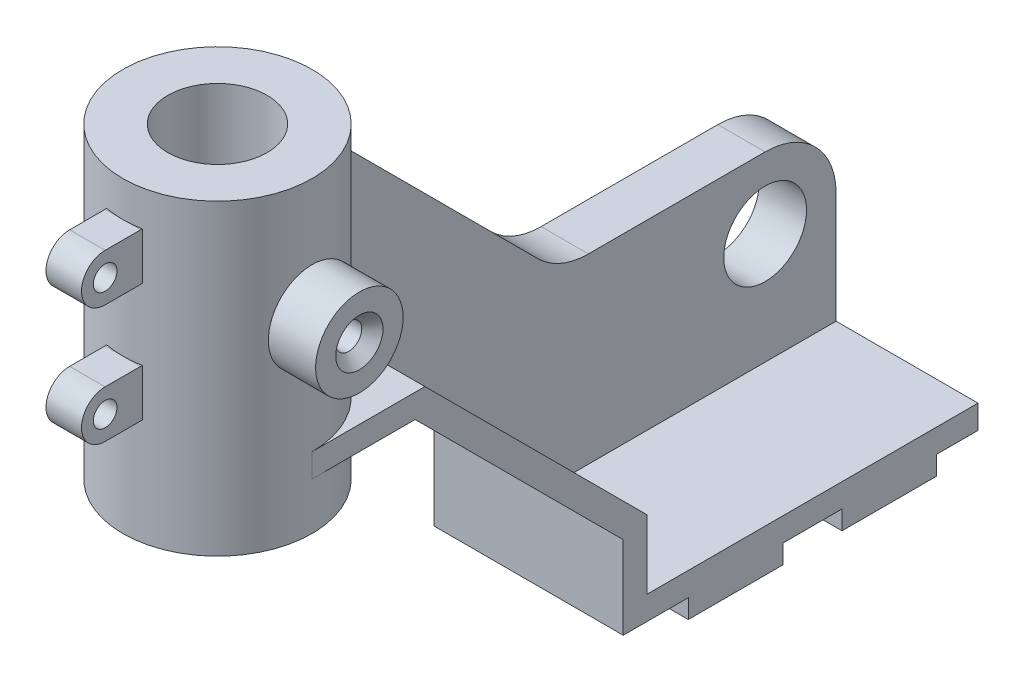
SolidWorks part; units mm, degrees
material "연성 주철 (SN)"
ref_plane "정면" through (0, 0, 0) normal (0, 0, 1) x (1, 0, 0)
ref_plane "윗면" through (0, 0, 0) normal (0, 1, 0) x (1, 0, 0)
ref_plane "우측면" through (0, 0, 0) normal (1, 0, 0) x (0, 0, -1)
sketch "Sketch1" plane through (0, 0, 0) normal (1, 0, 0) x (0, 0, -1)
  line L0 (-61.3727, 71.5352) -> (-13.6685, 71.5352)
  line L1 (-13.6685, 71.5352) -> (80.1894, -22.3227)
  line L2 (80.1894, -22.3227) -> (80.1894, -51.4648)
  line L3 (80.1894, -51.4648) -> (220.1894, -51.4648)
  line L4 (-61.3727, 61.5352) -> (-17.8106, 61.5352)
  line L5 (-17.8106, 61.5352) -> (70.1894, -26.4648)
  line L6 (70.1894, -26.4648) -> (70.1894, -61.4648)
  line L7 (70.1894, -61.4648) -> (220.1894, -61.4648)
  line L8 (-61.3727, 71.5352) -> (-61.3727, 61.5352)
  line L9 (220.1894, -51.4648) -> (220.1894, -61.4648)
  line L10 (150.1894, -66.0269) -> (150.1894, -44.0763) construction
  line L11 (97.6894, -58.9421) -> (137.6894, -58.9421)
  line L12 (97.6894, -58.9421) -> (97.6894, -69.4648)
  line L13 (97.6894, -69.4648) -> (137.6894, -69.4648)
  line L14 (137.6894, -58.9421) -> (137.6894, -69.4648)
  line L15 (162.6894, -58.9421) -> (202.6894, -58.9421)
  line L16 (162.6894, -58.9421) -> (162.6894, -69.4648)
  line L17 (162.6894, -69.4648) -> (202.6894, -69.4648)
  line L18 (202.6894, -58.9421) -> (202.6894, -69.4648)
  line L19 (137.6894, -66.0269) -> (162.6894, -66.0269)
  line L20 (7.0422, 121.5352) -> (103.0422, 25.5352)
  line L37 (220.1894, -51.4648) -> (220.1894, 25.5352)
  line L38 (220.1894, 25.5352) -> (103.0422, 25.5352)
  line L39 (7.0422, 121.5352) -> (-61.3727, 121.5352)
  line L41 (-61.3727, 121.5352) -> (-61.3727, 71.5352)
  point P23 (150.1894, -66.0269)
  point P24 (150.1894, -51.4648)
  point P26 (97.6894, -69.4648)
  point P27 (0, 0)
  point P28 (0, 0)
  point P29 (0, 0)
  point P35 (0, 0)
  point P37 (0, 0)
  dimension "D2" = 18
  dimension "D3" = 25
  dimension "D4" = 40
  dimension "D5" = 150
  dimension "D6" = 40
  dimension "D7" = 43
  dimension "D8" = 10
  dimension "D9" = 10
  dimension "D10" = 133
  dimension "D11" = 10
  dimension "D12" = 10
  dimension "D13" = 135
  dimension "D15" = 60
  dimension "D14" = 95
  dimension "D16" = 60
extrude "Boss-Extrude1" add sketch "Sketch1" along normal blind 80 contours L14 L7 L12 L13 | L7 L10 L3 L2 L1 L0 L8 L4 L5 L6 L12 L11 L14 | L10 L7 L16 L15 L18 L9 L3 | L18 L15 L16 L7 | L18 L7 L16 L17 | L14 L11 L12 L7 region at (0, 3.0174, -43.2698) region at (0, -55.8351, -185.6105) region at (0, -60.2035, -117.6894) region at (0, -65.4648, -117.6894) region at (0, -60.2035, -182.6894) region at (0, -65.4648, -182.6894)
extrude "Boss-Extrude2" add sketch "Sketch1<5>" along normal blind 20 contours L39 L41 L0 L1 L2 L3 L37 L38 L20 region at (0, 23.6569, -89.4101)
sketch "Sketch1<5>" plane through (0, 0, 0) normal (1, 0, 0) x (0, 0, -1) same geometry as "Sketch1"
fillet "Fillet1" radius 30 3 edges at (10, 25.5352, -220.1894) (10, 25.5352, -103.0422) (10, 121.5352, -7.0422)
hole_wizard "Ø25.0 (35) Diameter Hole1" positions "3DSketch1" profile "Sketch2" hole size "Ø25.0" standard "Ansi Metric" end condition up to next
sketch3d "3DSketch1"
  line L0 (0, -4.4648, -190.1894) -> (20, -4.4648, -190.1894) construction
  point P0 (20, -4.4648, -190.1894)
sketch "Sketch2" plane through (20, -4.4648, -190.1894) normal (0, 1, 0) x (0, 0, -1)
  line L0 (0, 0) -> (0, 20)
  line L1 (0, 20) -> (17.5, 20)
  line L2 (17.5, 20) -> (17.5, 0)
  line L5 (17.5, 0) -> (0, 0)
  line L11 (0, -6.35) -> (0, 107.95) construction
  dimension "관통 구멍 지름" = 35
  dimension "관통 구멍 깊이" = 20
sketch "Sketch3" plane through (0, 121.5352, 0) normal (0, 1, 0) x (1, 0, 0)
  line L0 (80, -61.3727) -> (20, -61.3727) construction
  line L1 (80, -61.3727) -> (80, -13.6685) construction
  circle A0 centre (40, -61.3727) radius 40
  dimension "D1" = 80
extrude "Boss-Extrude3" add sketch "Sketch3" along normal blind 50 and the other way blind 80
ref_plane "Plane1" through (40, 0, 0) normal (-1, 0, 0) x (0, 0, 1)
sketch "Sketch4" plane through (40, 0, 0) normal (-1, 0, 0) x (0, 0, 1)
  line L0 (101.3727, 146.5352) -> (116.3727, 146.5352) construction
  line L1 (101.3727, 41.5352) -> (101.3727, 171.5352) construction
  line L2 (101.3727, 156.5352) -> (116.3727, 156.5352)
  line L3 (101.3727, 136.5352) -> (116.3727, 136.5352)
  line L4 (101.3727, 96.5352) -> (116.3727, 96.5352) construction
  line L5 (101.3727, 106.5352) -> (116.3727, 106.5352)
  line L6 (101.3727, 86.5352) -> (116.3727, 86.5352)
  line L7 (21.3727, 41.5352) -> (101.3727, 41.5352) construction
  arc A0 (101.3727, 156.5352) -> (101.3727, 136.5352) centre (101.3727, 146.5352) ccw
  arc A1 (116.3727, 136.5352) -> (116.3727, 156.5352) centre (116.3727, 146.5352) ccw
  arc A2 (101.3727, 106.5352) -> (101.3727, 86.5352) centre (101.3727, 96.5352) ccw
  arc A3 (116.3727, 86.5352) -> (116.3727, 106.5352) centre (116.3727, 96.5352) ccw
  point P4 (108.8727, 146.5352)
  point P9 (108.8727, 96.5352)
  dimension "D3" = 10
  dimension "D4" = 10
  dimension "D1" = 55
  dimension "D2" = 50
  dimension "D5" = 15
  dimension "D6" = 15
extrude "Boss-Extrude4" add sketch "Sketch4" along normal mid plane 15
hole_wizard "Ø25.0 (42) Diameter Hole1" positions "3DSketch2" profile "Sketch5" hole size "Ø25.0" standard "Ansi Metric" end condition up to next
sketch3d "3DSketch2"
  line L0 (40, 41.5352, 61.3727) -> (40, 171.5352, 61.3727) construction
  point P0 (40, 171.5352, 61.3727)
sketch "Sketch5" plane through (40, 171.5352, 61.3727) normal (1, 0, 0) x (0, 0, 1)
  line L0 (0, 0) -> (0, 130)
  line L1 (0, 130) -> (21, 130)
  line L2 (21, 130) -> (21, 0)
  line L5 (21, 0) -> (0, 0)
  line L11 (0, -6.35) -> (0, 107.95) construction
  dimension "관통 구멍 지름" = 42
  dimension "관통 구멍 깊이" = 130
hole_wizard "Ø10.0 (10) Diameter Hole1" positions "3DSketch3" profile "Sketch6" hole size "Ø10.0" standard "Ansi Metric" end condition up to next
sketch3d "3DSketch3"
  line L0 (32.5, 146.5352, 116.3727) -> (47.5, 146.5352, 116.3727) construction
  line L1 (32.5, 96.5352, 116.3727) -> (47.5, 96.5352, 116.3727) construction
  point P0 (32.5, 146.5352, 116.3727)
  point P4 (32.5, 96.5352, 116.3727)
sketch "Sketch6" plane through (32.5, 146.5352, 116.3727) normal (0, 1, 0) x (0, 0, 1)
  line L0 (0, 0) -> (0, 15)
  line L1 (0, 15) -> (5, 15)
  line L2 (5, 15) -> (5, 0)
  line L5 (5, 0) -> (0, 0)
  line L11 (0, -6.35) -> (0, 107.95) construction
  dimension "관통 구멍 지름" = 10
  dimension "관통 구멍 깊이" = 15
sketch "Sketch7" plane through (80, 0, 0) normal (1, 0, 0) x (0, 0, -1)
  circle A0 centre (-61.3727, 121.5352) radius 18.5
  dimension "D1" = 37
extrude "Boss-Extrude5" add sketch "Sketch7" along normal blind 20 separate body
hole_wizard "CSK for M10 Flat Head Machine Screw1" positions "3DSketch4" profile "Sketch8" countersink size "M10" standard "Ansi Metric" end condition through all
sketch3d "3DSketch4"
  line L0 (100, 121.5352, 61.3727) -> (80, 121.5352, 61.3727) construction
  point P0 (100, 121.5352, 61.3727)
sketch "Sketch8" plane through (100, 121.5352, 61.3727) normal (0, 1, 0) x (0, 0, -1)
  line L0 (0, 0) -> (0, 100)
  line L1 (0, 100) -> (5.5, 100)
  line L2 (5.5, 100) -> (5.5, 4.5)
  line L3 (5.5, 4.5) -> (10, 0)
  line L5 (10, 0) -> (0, 0)
  line L6 (-5.5, 4.5) -> (-10, 0) construction
  line L11 (0, -6.35) -> (0, 107.95) construction
  dimension "관통 구멍 지름" = 11
  dimension "관통 구멍 깊이" = 100
  dimension "표면 카운터싱크 지름" = 20
  dimension "표면 카운터싱크 각도" = 90
